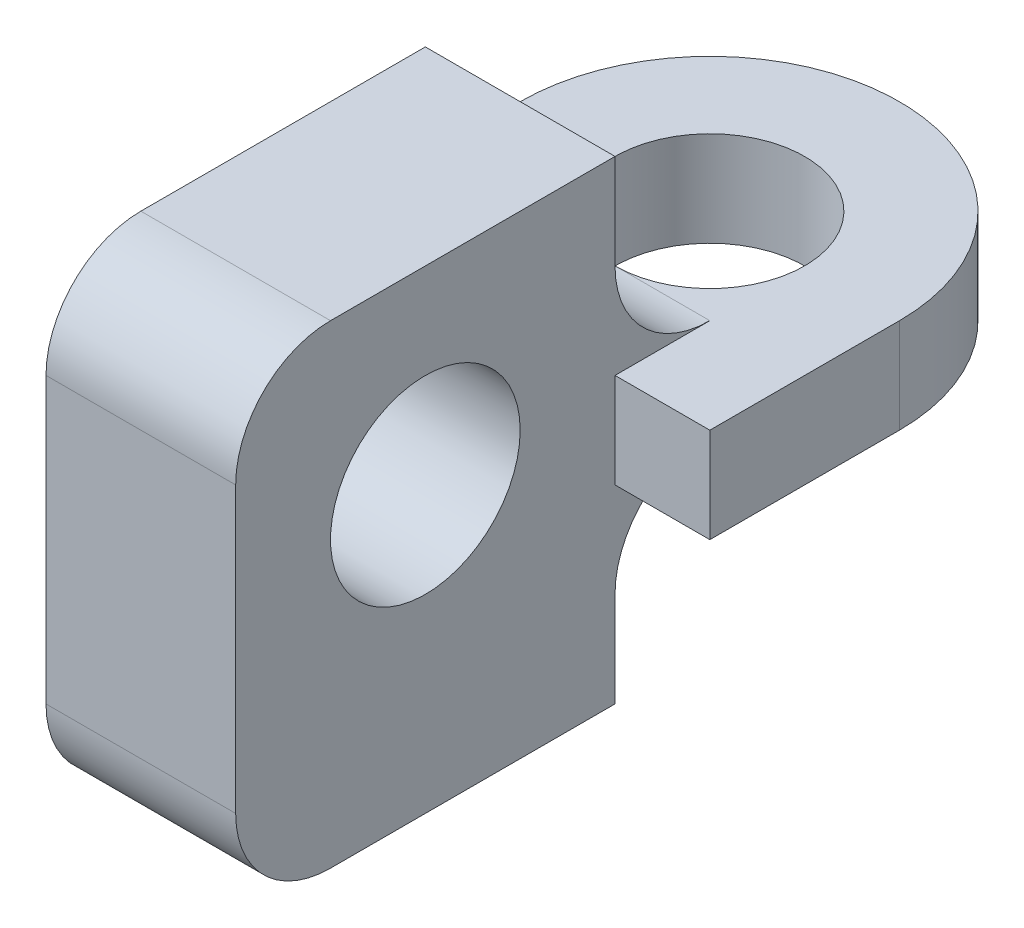
SolidWorks part; units mm, degrees
material "Cobre"
ref_plane "Alzado" through (0, 0, 0) normal (0, 0, 1) x (1, 0, 0)
ref_plane "Planta" through (0, 0, 0) normal (0, 1, 0) x (1, 0, 0)
ref_plane "Vista lateral" through (0, 0, 0) normal (1, 0, 0) x (0, 0, -1)
sketch "Croquis1" plane through (0, 0, 0) normal (1, 0, 0) x (0, 0, -1)
  line L1 (10, 0) -> (40, 0)
  line L2 (0, 10) -> (0, 40)
  line L3 (10, 50) -> (40, 50)
  line L4 (40, 0) -> (40, 50)
  arc A0 (0, 10) -> (10, 0) centre (10, 10) ccw
  arc A1 (10, 50) -> (0, 40) centre (10, 40) ccw
  point P7 (0, 0)
  point P10 (0, 50)
  dimension "D3" = 10
  dimension "D1" = 50
  dimension "D2" = 40
extrude "Saliente-Extruir1" add sketch "Croquis1" along normal blind 20
sketch "Croquis2" plane through (20, 0, 0) normal (1, 0, 0) x (0, 0, -1)
  line L0 (40, 50) -> (20, 50) construction
  line L1 (40, 50) -> (10, 50) construction
  line L2 (20, 50) -> (20, 30) construction
  circle A0 centre (20, 30) radius 10
extrude "Cortar-Extruir1" cut sketch "Croquis2" against normal blind 20
ref_plane "Plano1" through (0, 30, 0) normal (0, 1, 0) x (1, 0, 0)
sketch "Croquis6" plane through (0, 30, 0) normal (0, 1, 0) x (1, 0, 0)
  line L0 (0, 40) -> (10, 40) construction
  line L1 (20, 40) -> (0, 40) construction
  line L2 (10, 40) -> (10, 60) construction
  line L3 (-10, 60) -> (-10, 40)
  line L4 (-10, 40) -> (30, 40)
  line L5 (30, 40) -> (30, 60)
  arc A2 (30, 60) -> (-10, 60) centre (10, 60) ccw
extrude "Saliente-Extruir2" add sketch "Croquis6" against normal blind 10
sketch "Croquis8" plane through (0, 30, 0) normal (0, 1, 0) x (1, 0, 0)
  line L0 (10, 40) -> (10, 60) construction
  line L1 (0, 40) -> (20, 40) construction
  circle A0 centre (10, 60) radius 10
extrude "Cortar-Extruir2" cut sketch "Croquis8" against normal blind 10
fillet "Redondeo3" radius 10 1 edges at (10, 30, -40)
fillet "Redondeo4" radius 10 1 edges at (10, 20, -40)
